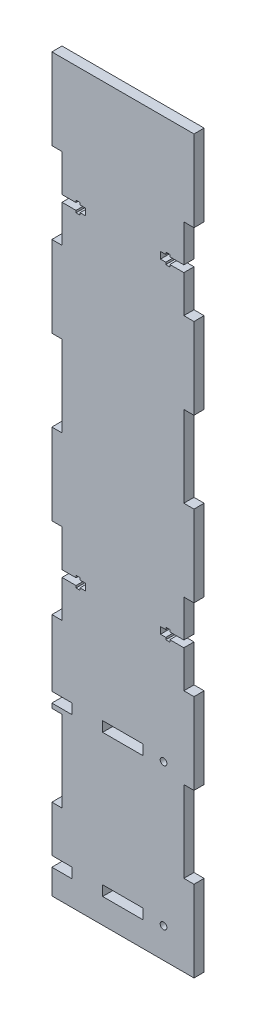
SolidWorks part; units mm, degrees
ref_plane "Front Plane" through (0, 0, 0) normal (0, 0, 1) x (1, 0, 0)
ref_plane "Top Plane" through (0, 0, 0) normal (0, 1, 0) x (1, 0, 0)
ref_plane "Right Plane" through (0, 0, 0) normal (1, 0, 0) x (0, 0, -1)
sketch "Sketch2" plane through (0, 0, 0) normal (0, 1, 0) x (0, 0, 1)
  line L1 (38.1, -44.45) -> (44.45, -44.45)
  line L2 (38.1, -44.45) -> (38.1, 44.45)
  line L3 (38.1, 44.45) -> (44.45, 44.45)
  line L4 (44.45, -44.45) -> (44.45, 44.45)
  dimension "D1" = 88.9
  dimension "D2" = 6.35
extrude "Boss-Extrude1" add sketch "Sketch2" along normal blind 457.2
ref_plane "Plane1" through (0, 0, 0) normal (1, 0, 0) x (0, 0, -1)
sketch "Sketch4" plane through (0, 0, 44.45) normal (0, 0, 1) x (1, 0, 0)
  line L0 (44.45, 457.2) -> (44.45, 406.4) construction
  line L1 (44.45, 457.2) -> (44.45, 0) construction
  line L2 (44.45, 406.4) -> (44.45, 355.6) construction
  line L3 (44.45, 355.6) -> (44.45, 304.8) construction
  line L4 (44.45, 304.8) -> (44.45, 254) construction
  line L5 (44.45, 254) -> (44.45, 203.2) construction
  line L6 (44.45, 203.2) -> (44.45, 152.4) construction
  line L7 (44.45, 152.4) -> (44.45, 101.6) construction
  line L8 (44.45, 101.6) -> (44.45, 50.8) construction
  line L9 (44.45, 50.8) -> (44.45, 0) construction
  line L11 (44.45, 406.4) -> (38.1, 406.4)
  line L12 (44.45, 406.4) -> (44.45, 355.6)
  line L13 (44.45, 355.6) -> (38.1, 355.6)
  line L14 (38.1, 406.4) -> (38.1, 355.6)
  line L15 (44.45, 304.8) -> (38.1, 304.8)
  line L16 (44.45, 304.8) -> (44.45, 254)
  line L17 (44.45, 254) -> (38.1, 254)
  line L18 (38.1, 304.8) -> (38.1, 254)
  line L19 (44.45, 203.2) -> (38.1, 203.2)
  line L20 (44.45, 203.2) -> (44.45, 152.4)
  line L21 (44.45, 152.4) -> (38.1, 152.4)
  line L22 (38.1, 203.2) -> (38.1, 152.4)
  line L23 (44.45, 101.6) -> (38.1, 101.6)
  line L24 (44.45, 101.6) -> (44.45, 50.8)
  line L25 (44.45, 50.8) -> (38.1, 50.8)
  line L26 (38.1, 101.6) -> (38.1, 50.8)
  dimension "D1" = 6.35
extrude "Cut-Extrude1" cut sketch "Sketch4" against normal through all
mirror "Mirror1" about plane through (0, 0, 0) normal (1, 0, 0) of "Cut-Extrude1"
sketch "Sketch5" plane through (0, 0, 38.1) normal (0, 0, -1) x (-1, 0, 0)
  line L0 (0, 0) -> (0, 124.5607) construction
  line L1 (-12.7, 110.8375) -> (12.7, 110.8375)
  line L2 (-12.7, 110.8375) -> (-12.7, 104.4875)
  line L3 (-12.7, 104.4875) -> (12.7, 104.4875)
  line L4 (12.7, 110.8375) -> (12.7, 104.4875)
  line L5 (-12.7, 21.9375) -> (12.7, 21.9375)
  line L6 (-12.7, 21.9375) -> (-12.7, 15.5875)
  line L7 (-12.7, 15.5875) -> (12.7, 15.5875)
  line L8 (12.7, 21.9375) -> (12.7, 15.5875)
  line L36 (38.1, 101.6) -> (44.45, 101.6)
  line L37 (44.45, 101.6) -> (44.45, 152.4)
  line L38 (44.45, 152.4) -> (38.1, 152.4)
  line L39 (38.1, 152.4) -> (38.1, 203.2)
  line L40 (38.1, 203.2) -> (44.45, 203.2)
  line L41 (44.45, 203.2) -> (44.45, 254)
  line L42 (44.45, 254) -> (38.1, 254)
  line L43 (38.1, 254) -> (38.1, 304.8)
  line L44 (38.1, 304.8) -> (44.45, 304.8)
  line L45 (44.45, 304.8) -> (44.45, 355.6)
  line L46 (44.45, 355.6) -> (38.1, 355.6)
  line L47 (38.1, 355.6) -> (38.1, 406.4)
  line L48 (38.1, 406.4) -> (44.45, 406.4)
  line L49 (44.45, 406.4) -> (44.45, 457.2)
  line L50 (44.45, 457.2) -> (-44.45, 457.2)
  line L51 (-44.45, 457.2) -> (-44.45, 406.4)
  line L52 (-44.45, 406.4) -> (-38.1, 406.4)
  line L53 (-38.1, 406.4) -> (-38.1, 355.6)
  line L54 (-38.1, 355.6) -> (-44.45, 355.6)
  line L55 (-44.45, 355.6) -> (-44.45, 304.8)
  line L56 (-44.45, 304.8) -> (-38.1, 304.8)
  line L57 (-38.1, 304.8) -> (-38.1, 254)
  line L58 (-38.1, 254) -> (-44.45, 254)
  line L59 (-44.45, 254) -> (-44.45, 203.2)
  line L60 (-44.45, 203.2) -> (-38.1, 203.2)
  line L61 (-38.1, 203.2) -> (-38.1, 152.4)
  line L62 (-38.1, 152.4) -> (-44.45, 152.4)
  line L63 (-44.45, 152.4) -> (-44.45, 101.6)
  line L64 (-44.45, 101.6) -> (-38.1, 101.6)
  line L65 (-38.1, 101.6) -> (-38.1, 50.8)
  line L66 (-38.1, 50.8) -> (-44.45, 50.8)
  line L67 (-44.45, 50.8) -> (-44.45, 0)
  line L68 (-44.45, 0) -> (44.45, 0)
  line L69 (44.45, 0) -> (44.45, 50.8)
  line L70 (44.45, 50.8) -> (38.1, 50.8)
  line L71 (38.1, 50.8) -> (38.1, 101.6)
  line L72 (38.1, 101.6) -> (44.45, 101.6)
  line L73 (44.45, 101.6) -> (44.45, 152.4)
  line L74 (44.45, 152.4) -> (38.1, 152.4)
  line L75 (38.1, 152.4) -> (38.1, 203.2)
  line L76 (38.1, 203.2) -> (44.45, 203.2)
  line L77 (44.45, 203.2) -> (44.45, 254)
  line L78 (44.45, 254) -> (38.1, 254)
  line L79 (38.1, 254) -> (38.1, 304.8)
  line L80 (38.1, 304.8) -> (44.45, 304.8)
  line L81 (44.45, 304.8) -> (44.45, 355.6)
  line L82 (44.45, 355.6) -> (38.1, 355.6)
  line L83 (38.1, 355.6) -> (38.1, 406.4)
  line L84 (38.1, 406.4) -> (44.45, 406.4)
  line L85 (44.45, 406.4) -> (44.45, 457.2)
  line L86 (44.45, 457.2) -> (-44.45, 457.2)
  line L87 (-44.45, 457.2) -> (-44.45, 406.4)
  line L88 (-44.45, 406.4) -> (-38.1, 406.4)
  line L89 (-38.1, 406.4) -> (-38.1, 355.6)
  line L90 (-38.1, 355.6) -> (-44.45, 355.6)
  line L91 (-44.45, 355.6) -> (-44.45, 304.8)
  line L92 (-44.45, 304.8) -> (-38.1, 304.8)
  line L93 (-38.1, 304.8) -> (-38.1, 254)
  line L94 (-38.1, 254) -> (-44.45, 254)
  line L95 (-44.45, 254) -> (-44.45, 203.2)
  line L96 (-44.45, 203.2) -> (-38.1, 203.2)
  line L97 (-38.1, 203.2) -> (-38.1, 152.4)
  line L98 (-38.1, 152.4) -> (-44.45, 152.4)
  line L99 (-44.45, 152.4) -> (-44.45, 101.6)
  line L100 (-44.45, 101.6) -> (-38.1, 101.6)
  line L101 (-38.1, 101.6) -> (-38.1, 50.8)
  line L102 (-38.1, 50.8) -> (-44.45, 50.8)
  line L103 (-44.45, 50.8) -> (-44.45, 0)
  line L104 (-44.45, 0) -> (44.45, 0)
  line L105 (44.45, 0) -> (44.45, 50.8)
  line L106 (44.45, 50.8) -> (38.1, 50.8)
  line L107 (38.1, 50.8) -> (38.1, 101.6)
  dimension "D2" = 6.35
  dimension "D3" = 6.35
  dimension "D4" = 25.4
  dimension "D5" = 25.4
  dimension "D6" = 82.55
  dimension "D7" = 15.5875
  dimension "D1" = 0
extrude "Cut-Extrude2" cut sketch "Sketch5" against normal through all contours L0 L7 L8 L5 | L7 L0 L5 L6 | L0 L3 L4 L1 | L3 L0 L1 L2 region at (6.35, 107.6625, 38.1) region at (-6.35, 107.6625, 38.1) region at (6.35, 18.7625, 38.1) region at (-6.35, 18.7625, 38.1)
sketch "Sketch6" plane through (0, 0, 44.45) normal (0, 0, 1) x (1, 0, 0)
  line L0 (25.4, 107.6625) -> (-25.4, 107.6625) construction
  line L1 (12.7, 110.8375) -> (-12.7, 110.8375) construction
  line L2 (12.7, 104.4875) -> (-12.7, 104.4875) construction
  line L3 (-25.4, 18.7625) -> (25.4, 18.7625) construction
  line L4 (12.7, 21.9375) -> (-12.7, 21.9375) construction
  line L5 (12.7, 15.5875) -> (-12.7, 15.5875) construction
  line L6 (0, 132.4794) -> (0, 71.8673) construction
  line L7 (-12.7, 110.8375) -> (-12.7, 104.4875) construction
  line L8 (12.7, 110.8375) -> (12.7, 104.4875) construction
  circle A0 centre (25.4, 107.6625) radius 2.0955
  circle A3 centre (25.4, 18.7625) radius 2.0955
  dimension "D1" = 4.191
  dimension "D2" = 12.7
extrude "Cut-Extrude3" cut sketch "Sketch6" against normal through all
sketch "Sketch7" plane through (0, 0, 38.1) normal (0, 0, -1) x (-1, 0, 0)
  line L0 (44.45, 152.4) -> (44.45, 101.6) construction
  line L1 (31.75, 110.8375) -> (44.45, 110.8375)
  line L2 (31.75, 110.8375) -> (31.75, 104.4875)
  line L3 (31.75, 104.4875) -> (44.45, 104.4875)
  line L4 (44.45, 110.8375) -> (44.45, 104.4875)
extrude "Cut-Extrude4" cut sketch "Sketch7" against normal blind 10
sketch "Sketch8" plane through (0, 0, 38.1) normal (0, 0, -1) x (-1, 0, 0)
  line L0 (44.45, 50.8) -> (44.45, 0) construction
  line L1 (31.75, 21.9375) -> (44.45, 21.9375)
  line L2 (31.75, 21.9375) -> (31.75, 15.5875)
  line L3 (31.75, 15.5875) -> (44.45, 15.5875)
  line L4 (44.45, 21.9375) -> (44.45, 15.5875)
extrude "Cut-Extrude5" cut sketch "Sketch8" against normal through all
sketch "Sketch9" plane through (0, 0, 44.45) normal (0, 0, 1) x (1, 0, 0)
  line L0 (0, 457.2) -> (0, 0) construction
  line L1 (-44.45, 457.2) -> (44.45, 457.2) construction
  line L2 (-38.1, 406.4) -> (-38.1, 355.6) construction
  line L3 (-38.1, 381) -> (-21.5952, 381) construction
  line L4 (-38.1, 177.8) -> (-21.5952, 177.8) construction
  line L5 (-38.1, 203.2) -> (-38.1, 152.4) construction
  line L6 (38.1, 177.8) -> (21.5952, 177.8) construction
  line L7 (38.1, 381) -> (21.5952, 381) construction
  line B0 (-38.1, 383.0955) -> (-38.1, 378.9045)
  line B1 (-26.797, 378.9045) -> (-26.797, 377.571)
  line B2 (-26.797, 377.571) -> (-29.337, 377.571)
  line B3 (-29.337, 377.571) -> (-29.337, 378.9045)
  line B4 (-29.337, 378.9045) -> (-38.1, 378.9045)
  line B5 (-26.797, 378.9045) -> (-23.495, 378.9045)
  line B6 (-23.495, 378.9045) -> (-23.495, 383.0955)
  line B7 (-26.797, 383.0955) -> (-23.495, 383.0955)
  line B8 (-29.337, 383.0955) -> (-38.1, 383.0955)
  line B9 (-29.337, 384.429) -> (-29.337, 383.0955)
  line B10 (-26.797, 384.429) -> (-29.337, 384.429)
  line B11 (-26.797, 383.0955) -> (-26.797, 384.429)
  line B12 (-38.1, 179.8955) -> (-38.1, 175.7045)
  line B13 (-26.797, 175.7045) -> (-26.797, 174.371)
  line B14 (-26.797, 174.371) -> (-29.337, 174.371)
  line B15 (-29.337, 174.371) -> (-29.337, 175.7045)
  line B16 (-29.337, 175.7045) -> (-38.1, 175.7045)
  line B17 (-26.797, 175.7045) -> (-23.495, 175.7045)
  line B18 (-23.495, 175.7045) -> (-23.495, 179.8955)
  line B19 (-26.797, 179.8955) -> (-23.495, 179.8955)
  line B20 (-29.337, 179.8955) -> (-38.1, 179.8955)
  line B21 (-29.337, 181.229) -> (-29.337, 179.8955)
  line B22 (-26.797, 181.229) -> (-29.337, 181.229)
  line B23 (-26.797, 179.8955) -> (-26.797, 181.229)
  line B24 (38.1, 383.0955) -> (38.1, 378.9045)
  line B25 (26.797, 378.9045) -> (26.797, 377.571)
  line B26 (26.797, 377.571) -> (29.337, 377.571)
  line B27 (29.337, 377.571) -> (29.337, 378.9045)
  line B28 (29.337, 378.9045) -> (38.1, 378.9045)
  line B29 (26.797, 378.9045) -> (23.495, 378.9045)
  line B30 (23.495, 378.9045) -> (23.495, 383.0955)
  line B31 (26.797, 383.0955) -> (23.495, 383.0955)
  line B32 (29.337, 383.0955) -> (38.1, 383.0955)
  line B33 (29.337, 384.429) -> (29.337, 383.0955)
  line B34 (26.797, 384.429) -> (29.337, 384.429)
  line B35 (26.797, 383.0955) -> (26.797, 384.429)
  line B36 (38.1, 179.8955) -> (38.1, 175.7045)
  line B37 (26.797, 175.7045) -> (26.797, 174.371)
  line B38 (26.797, 174.371) -> (29.337, 174.371)
  line B39 (29.337, 174.371) -> (29.337, 175.7045)
  line B40 (29.337, 175.7045) -> (38.1, 175.7045)
  line B41 (26.797, 175.7045) -> (23.495, 175.7045)
  line B42 (23.495, 175.7045) -> (23.495, 179.8955)
  line B43 (26.797, 179.8955) -> (23.495, 179.8955)
  line B44 (29.337, 179.8955) -> (38.1, 179.8955)
  line B45 (29.337, 181.229) -> (29.337, 179.8955)
  line B46 (26.797, 181.229) -> (29.337, 181.229)
  line B47 (26.797, 179.8955) -> (26.797, 181.229)
sketch_block_instance "TSlot-1"
sketch_block "TSlot" parameters "D1"=3.302, "D2"=2.54, "D3"=3.175, "D4"=8.763, "D5"=1.3462
sketch_block_instance "TSlot-3"
sketch_block_instance "TSlot-4"
sketch_block_instance "TSlot-5"
extrude "Cut-Extrude6" cut sketch "Sketch9" against normal through all
